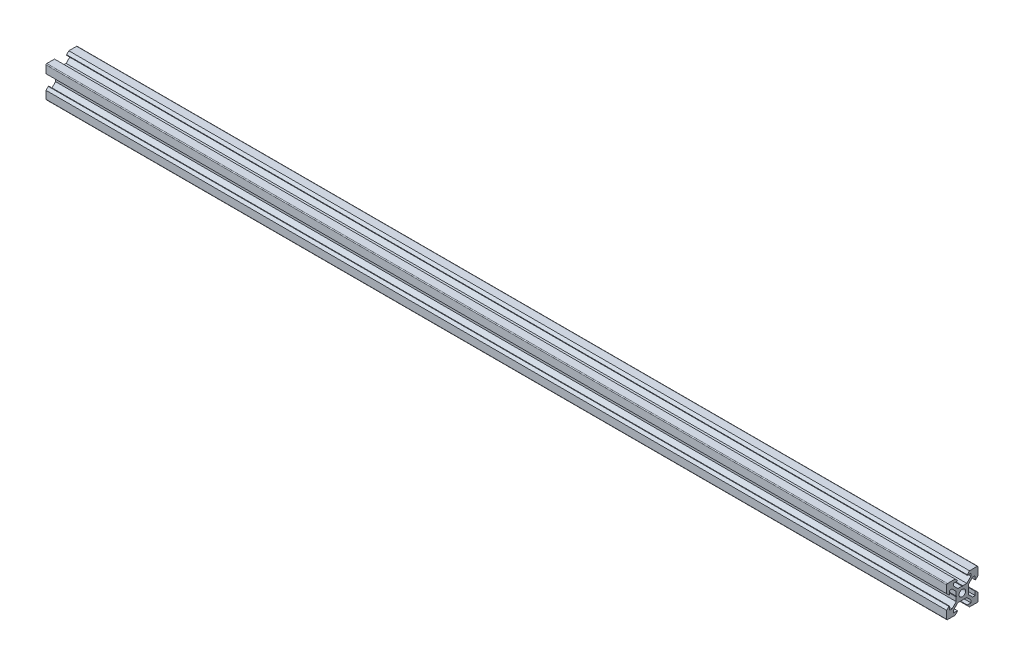
SolidWorks part; units mm, degrees
material "6061-T6 (SS)"
ref_plane "Top" through (0, 0, 0) normal (0, 0, 1) x (1, 0, 0)
ref_plane "Front" through (0, 0, 0) normal (0, 1, 0) x (1, 0, 0)
ref_plane "Right" through (0, 0, 0) normal (1, 0, 0) x (0, 0, -1)
sketch "Profile Sketch" plane through (0, 0, 0) normal (1, 0, 0) x (0, 0, -1)
  line L0 (-0.5, 10) -> (-5.42, 10)
  line L1 (-4.5, 8.2) -> (-4.5, 6.56)
  line L2 (-4.5, 6.56) -> (-7.16, 3.9)
  line L3 (-7.16, 3.9) -> (-9.79, 3.9)
  line L4 (-9.79, 3.9) -> (-10, 3.69)
  line L7 (-3.4387, 5.5) -> (-6.1, 2.8387)
  line L8 (-6.1, 2.8387) -> (-6.1, -0.21)
  line L9 (-6.875, 8.545) -> (-6.875, 8.2)
  line L10 (-6.875, 8.2) -> (-4.5, 8.2)
  line L11 (-6.875, 8.545) -> (-5.42, 10)
  line L12 (0, -10) -> (0, 10) construction
  line L13 (-20, 0) -> (20, 0) construction
  line L14 (-10, -10) -> (-10, 10) construction
  line L15 (-6.875, -8.545) -> (-5.42, -10)
  line L16 (-6.875, -8.2) -> (-4.5, -8.2)
  line L17 (-6.875, -8.545) -> (-6.875, -8.2)
  line L18 (-3.44, -5.5) -> (-6.1, -2.8387)
  line L21 (-7.16, -3.9) -> (-9.79, -3.9)
  line L22 (-4.5, -6.56) -> (-7.16, -3.9)
  line L23 (-4.5, -8.2) -> (-4.5, -6.56)
  line L24 (-0.5, -10) -> (-5.42, -10)
  line L25 (-10, 0) -> (-20, 10) construction
  line L26 (-18.545, 3.125) -> (-18.2, 3.125)
  line L27 (-13.125, -8.545) -> (-13.125, -8.2)
  line L28 (-13.125, -8.2) -> (-15.5, -8.2)
  line L29 (-13.125, -8.545) -> (-14.58, -10)
  line L30 (-15.5, -8.2) -> (-15.5, -6.56)
  line L31 (-15.5, -6.56) -> (-12.84, -3.9)
  line L32 (-12.84, -3.9) -> (-10.21, -3.9)
  line L33 (-20, 4.58) -> (-20, 9.5)
  line L34 (-13.9, 2.8387) -> (-13.9, 0.21)
  line L35 (-16.56, 5.5) -> (-13.9, 2.8387)
  line L36 (-12.84, 3.9) -> (-10.21, 3.9)
  line L37 (-15.5, 6.56) -> (-12.84, 3.9)
  line L38 (-15.5, 8.2) -> (-15.5, 6.56)
  line L39 (-13.125, 8.545) -> (-14.58, 10)
  line L40 (-13.125, 8.2) -> (-15.5, 8.2)
  line L41 (-13.125, 8.545) -> (-13.125, 8.2)
  line L42 (-18.2, 3.125) -> (-18.2, 5.5)
  line L43 (-18.545, 3.125) -> (-20, 4.58)
  line L44 (-18.2, 5.5) -> (-16.56, 5.5)
  line L45 (-14.58, 10) -> (-19.5, 10)
  line L46 (-16.56, -5.5) -> (-13.9, -2.8387)
  line L47 (-14.58, -10) -> (-19.5, -10)
  line L48 (-18.2, -5.5) -> (-16.56, -5.5)
  line L49 (-18.545, -3.125) -> (-20, -4.58)
  line L50 (-18.2, -3.125) -> (-18.2, -5.5)
  line L51 (-20, -4.58) -> (-20, -9.5)
  line L52 (-18.545, -3.125) -> (-18.2, -3.125)
  line L53 (10, -10) -> (10, 10) construction
  line L99 (-10, 3.69) -> (-10.21, 3.9)
  line L100 (-10, -3.69) -> (-10.21, -3.9)
  line L101 (-9.79, -3.9) -> (-10, -3.69)
  line L102 (-13.9, -0.21) -> (-13.69, 0)
  line L103 (-13.69, 0) -> (-13.9, 0.21)
  line L104 (-13.9, -0.21) -> (-13.9, -2.8387)
  line L105 (-6.1, -0.21) -> (-6.31, 0)
  line L106 (-6.31, 0) -> (-6.1, -0.21)
  line L107 (-6.1, -0.21) -> (-6.1, -2.8387)
  line L117 (-5.42, -10) -> (-0.5, -10)
  line L118 (20, -10) -> (20, 10) construction
  line L119 (20, -10) -> (-20, -10) construction
  line L120 (-20, -10) -> (-20, 10) construction
  line L121 (20, 10) -> (-20, 10) construction
  line L122 (20, -10) -> (-20, 10) construction
  line L123 (-20, -10) -> (20, 10) construction
  line L124 (-5.42, 10) -> (-0.5, 10)
  line L125 (-1.455, 3.125) -> (-1.8, 3.125)
  line L126 (-1.455, -3.125) -> (-1.8, -3.125)
  line L127 (-1.8, -5.5) -> (-3.44, -5.5)
  line L128 (-1.8, 5.5) -> (-3.44, 5.5)
  line L129 (-1.8, 3.125) -> (-1.8, 5.5)
  line L130 (-1.8, -3.125) -> (-1.8, -5.5)
  line L131 (0, -4.58) -> (0, -9.5)
  line L132 (0, 4.58) -> (0, 9.5)
  line L133 (-1.455, 3.125) -> (0, 4.58)
  line L134 (-1.455, -3.125) -> (0, -4.58)
  circle A0 centre (-10, 0) radius 2.1
  arc A1 (-19.5, 10) -> (-20, 9.5) centre (-19.5, 9.5) ccw
  arc A2 (-19.5, -10) -> (-20, -9.5) centre (-19.5, -9.5) cw
  arc A3 (-0.5, -10) -> (0, -9.5) centre (-0.5, -9.5) ccw
  arc A4 (-0.5, 10) -> (0, 9.5) centre (-0.5, 9.5) cw
  point P2 (-17.38, 5.5)
  point P35 (-2.4957, 0)
  point P76 (-2.62, 5.5)
  point P108 (0, -8.2)
  point P119 (0, 8.2)
  point P131 (0, 0)
  point P143 (0, 0)
  dimension "D4" = 5.42
  dimension "D5" = 40
  dimension "D6" = 4.2
  dimension "D16" = 0.5
  dimension "D1" = 0.21
  dimension "D2" = 45
  dimension "D3" = 20
  dimension "D7" = 1.5
  dimension "D8" = 1.8
  dimension "D9" = 10
  dimension "D10" = 3.9
  dimension "D11" = 3.9
  dimension "D13" = 3.125
  dimension "D14" = 5.5
  dimension "D15" = 1.64
extrude "Profile Extrude" add sketch "Profile Sketch" along normal blind 575 contours L126 L0 L11 L9 L10 L1 L2 L3 L4 L99 L36 L37 L38 L40 L41 L39 L45 A1 L33 L43 L26 L42 L44 L35 L34 L103 L102 L104 L46 L48 L50 L52 L49 L51 A2 L47 region at (0, 9.6536, 0.3464)
equation "\"M8x1.25_Close_Hole\"= 8.4"
